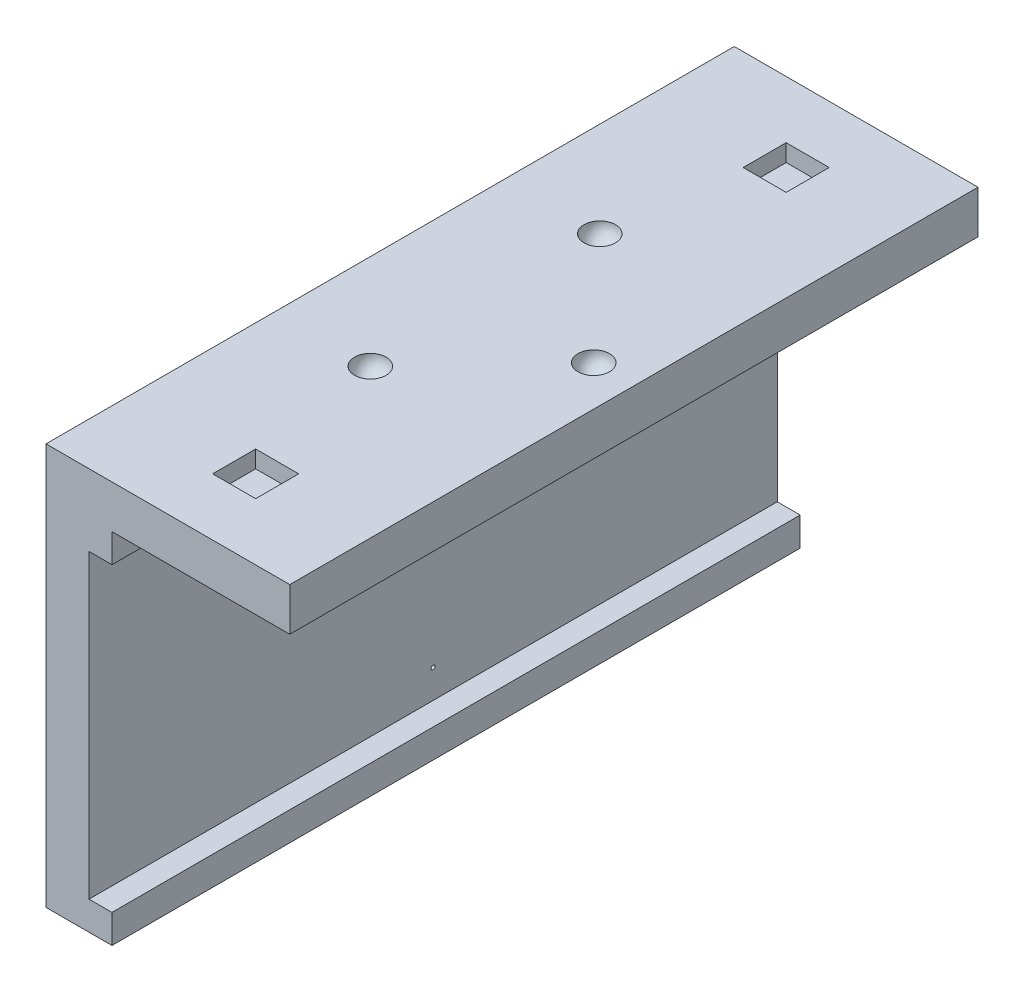
SolidWorks part; units mm, degrees
ref_plane "Front Plane" through (0, 0, 0) normal (0, 0, 1) x (1, 0, 0)
ref_plane "Top Plane" through (0, 0, 0) normal (0, 1, 0) x (1, 0, 0)
ref_plane "Right Plane" through (0, 0, 0) normal (1, 0, 0) x (0, 0, -1)
sketch "Sketch1" plane through (0, 0, 0) normal (0, 0, 1) x (1, 0, 0)
  line L0 (0, 0) -> (0, -70)
  line L1 (0, 0) -> (42.5, 0)
  line L2 (0, -70) -> (7.5, -70)
  line L3 (42.5, 0) -> (42.5, -7.5)
  line L4 (42.5, -7.5) -> (7.5, -7.5)
  line L5 (7.5, -7.5) -> (7.5, -70)
extrude "Boss-Extrude1" add sketch "Sketch1" along normal blind 120
sketch "Sketch3" plane through (0, 0, 0) normal (-1, 0, 0) x (0, 0, 1)
  line L1 (120, 0) -> (120, -70) construction
  line L2 (120, -60) -> (0, -60) construction
  line L3 (0, 0) -> (0, -70) construction
  circle A0 centre (60, -60) radius 0.35
sketch "Sketch5" plane through (7.5, 0, 0) normal (1, 0, 0) x (0, 0, -1)
  line L0 (-120, -70) -> (-120, -7.5) construction
  line L1 (0, -70) -> (-120, -70)
  line L2 (0, -70) -> (0, -65)
  line L3 (0, -65) -> (-120, -65)
  line L4 (-120, -70) -> (-120, -65)
  line L5 (0, -70) -> (0, -7.5) construction
  line L6 (-120, -7.5) -> (0, -7.5)
  line L7 (-120, -7.5) -> (-120, -12.5)
  line L8 (-120, -12.5) -> (0, -12.5)
  line L9 (0, -7.5) -> (0, -12.5)
  dimension "D1" = 5
  dimension "D2" = 5
extrude "Boss-Extrude2" add sketch "Sketch5" along normal blind 4
sketch "Sketch7" plane through (0, 0, 0) normal (0, 1, 0) x (1, 0, 0)
  line L0 (0, -60) -> (22.8039, -60) construction
  line L1 (0, -120) -> (0, 0) construction
  line L2 (22.8039, -60) -> (22.8039, -106.25) construction
  line L4 (19.0539, -102.5) -> (26.5539, -102.5)
  line L5 (19.0539, -102.5) -> (19.0539, -110)
  line L6 (19.0539, -110) -> (26.5539, -110)
  line L7 (26.5539, -102.5) -> (26.5539, -110)
  line L8 (19.0539, -102.5) -> (26.5539, -110) construction
  line L9 (19.0539, -110) -> (26.5539, -102.5) construction
  dimension "D1" = 7.5
  dimension "D2" = 7.5
extrude "Cut-Extrude3" cut sketch "Sketch7" against normal blind 3
ref_plane "Plane1" through (0, 0, 60) normal (0, 0, 1) x (1, 0, 0)
sketch "Sketch10" plane through (0, 0, 0) normal (0, 1, 0) x (1, 0, 0)
  line L0 (38.25, -60) -> (32.75, -60)
  arc A0 (32.75, -60) -> (38.25, -60) centre (35.5, -60) ccw
revolve "Cut-Revolve6" cut sketch "Sketch10" angle 360 about L0 reverse direction yes
sketch "Sketch11" plane through (0, 0, 0) normal (0, 1, 0) x (1, 0, 0)
  line L0 (19.3039, -40) -> (13.8039, -40)
  arc A0 (13.8039, -40) -> (19.3039, -40) centre (16.5539, -40) ccw
revolve "Cut-Revolve7" cut sketch "Sketch11" angle 360 about L0
mirror "Mirror3" about plane through (0, 0, 60) normal (0, 0, 1) of "Cut-Extrude3", "Cut-Revolve7"
extrude "Cut-Extrude4" cut sketch "Sketch3" against normal through all
sketch "Sketch12" plane through (7.5, 0, 0) normal (1, 0, 0) x (0, 0, -1)
  circle A0 centre (-60, -35) radius 2.5
extrude "Boss-Extrude3" add sketch "Sketch12" along normal blind 4
thread "Thread1" pitch 0.3175 method cut profile "Thread Profile1" start angle 0, offset 0, length 5, pitch 0.3175, diameter 5
ref_plane "Plane2" through (11.5, -35, 62.5) normal (0, -1, 0) x (0, 0, 1)
sketch "Thread Profile1" plane through (11.5, -35, 62.5) normal (0, -1, 0) x (0, 0, 1)
  line L0 (0, 0) -> (0, 0.3175) construction
  line L11 (0, 0) -> (0, 0.2778)
  line L12 (0, 0.2778) -> (-0.1719, 0.1786)
  line L13 (-0.1719, 0.1786) -> (-0.1719, 0.0992)
  line L15 (-0.1719, 0.0992) -> (0, 0)
  line L17 (-0.1719, 0.1389) -> (0, 0.1389) construction
  point P2 (0, 0)
  dimension "Pitch" = 0.3175
  dimension "Profile_Angle" = 60
  dimension "Profile_Land" = 0.0794
  dimension "Profile_Height" = 0.1719
